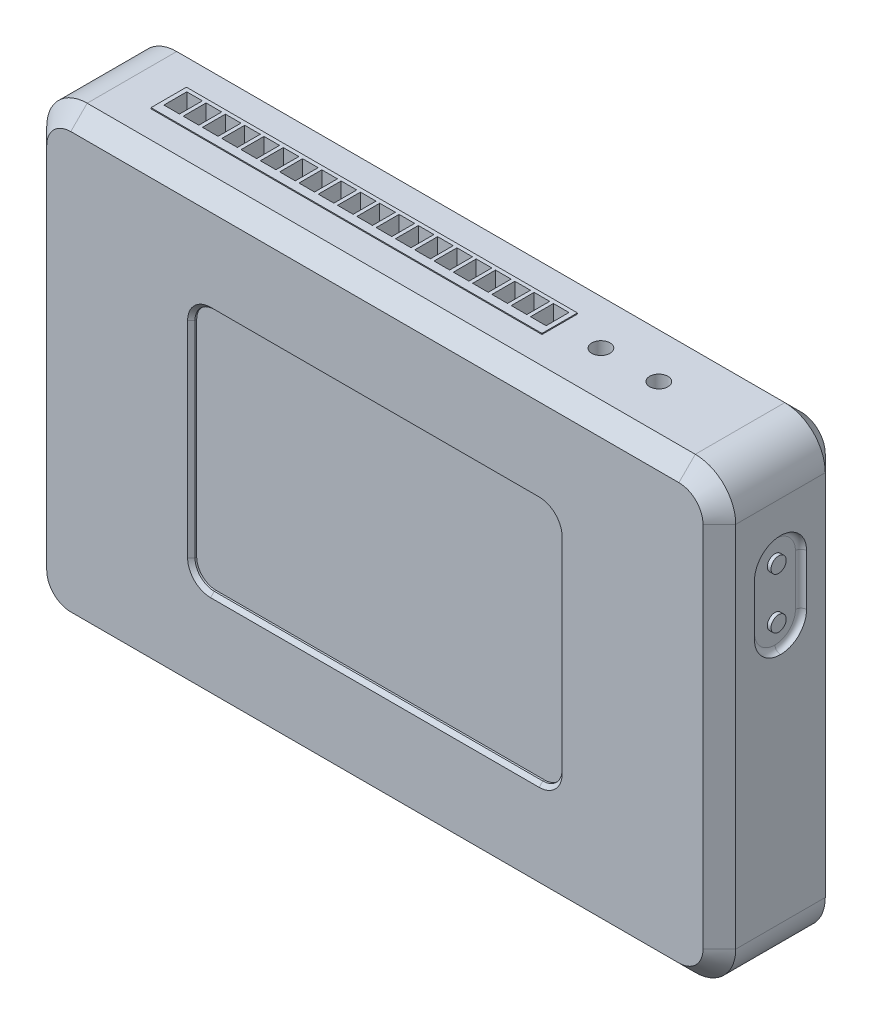
SolidWorks part; units mm, degrees
ref_plane "Top Plane" through (0, 0, 0) normal (0, 0, 1) x (1, 0, 0)
ref_plane "Front Plane" through (0, 0, 0) normal (0, 1, 0) x (1, 0, 0)
ref_plane "Right Plane" through (0, 0, 0) normal (1, 0, 0) x (0, 0, -1)
sketch "Sketch1" plane through (0, 0, 0) normal (0, 0, 1) x (1, 0, 0)
  line L1 (-68.0234, -44.3061) -> (68.0234, -44.3061)
  line L2 (-68.0234, -44.3061) -> (-68.0234, 44.3061)
  line L3 (-68.0234, 44.3061) -> (68.0234, 44.3061)
  line L4 (68.0234, -44.3061) -> (68.0234, 44.3061)
  line L5 (-68.0234, -44.3061) -> (68.0234, 44.3061) construction
  line L6 (-68.0234, 44.3061) -> (68.0234, -44.3061) construction
  point P0 (0, 0)
  dimension "D1" = 88.6122
  dimension "D2" = 136.0469
extrude "Boss-Extrude1" add sketch "Sketch1" along normal mid plane 24.1427
fillet "Fillet1" radius 7.9882 4 edges at (-68.0234, -44.3061, 0) (-68.0234, 44.3061, 0) (68.0234, 44.3061, 0) (68.0234, -44.3061, 0)
chamfer "Chamfer1" distance 3.2329 angle 45 16 edges at (0, 44.3061, -12.0713) (-65.6837, 41.9664, -12.0713) (65.6837, 41.9664, -12.0713) (-68.0234, 0, -12.0713) (68.0234, 0, -12.0713) (-65.6837, -41.9664, -12.0713) (65.6837, -41.9664, -12.0713) (0, -44.3061, -12.0713) (0, 44.3061, 12.0713) (-65.6837, 41.9664, 12.0713) (65.6837, 41.9664, 12.0713) (-68.0234, 0, 12.0713) (68.0234, 0, 12.0713) (-65.6837, -41.9664, 12.0713) (65.6837, -41.9664, 12.0713) (0, -44.3061, 12.0713)
sketch "Sketch2" plane through (68.0234, 0, 0) normal (1, 0, 0) x (0, 0, -1)
  line L0 (0, 0) -> (0, 50000) construction
  line L1 (5.1435, 9.6288) -> (-5.1435, 9.6288)
  line L2 (5.1435, 9.6288) -> (5.1435, 29.9743)
  line L3 (5.1435, 29.9743) -> (-5.1435, 29.9743)
  line L4 (-5.1435, 9.6288) -> (-5.1435, 29.9743)
  line L5 (5.1435, 9.6288) -> (-5.1435, 29.9743) construction
  line L6 (5.1435, 29.9743) -> (-5.1435, 9.6288) construction
  line L7 (8.8385, -44.3061) -> (-8.8385, -44.3061) construction
  line L8 (8.8385, -44.3061) -> (-8.8385, -44.3061) construction
  circle A0 centre (0, 14.7723) radius 1.5 construction
  arc A1 (-5.1435, 14.7723) -> (0, 9.6288) centre (0, 14.7723) ccw construction
  point P0 (0, 19.8015)
  point P14 (-5.1435, 16.5564)
  dimension "D3" = 3
  dimension "D1" = 10.287
  dimension "D2" = 64.1076
  dimension "D4" = 5.0292
extrude "Cut-Extrude1" cut sketch "Sketch2" against normal blind 1.1006
fillet "Fillet2" radius 5.1435 4 edges at (67.4731, 9.6288, -5.1435) (67.4731, 29.9743, -5.1435) (67.4731, 29.9743, 5.1435) (67.4731, 9.6288, 5.1435)
fillet "Fillet3" radius 1.1006 6 edges at (66.9228, 28.4678, 3.637) (66.9228, 28.4678, -3.637) (66.9228, 19.8015, -5.1435) (66.9228, 11.1353, -3.637) (66.9228, 11.1353, 3.637) (66.9228, 19.8015, 5.1435)
sketch "Sketch3" plane through (66.9228, 0, 0) normal (1, 0, 0) x (0, 0, -1)
  line L0 (0, 0) -> (0, 24.8307) construction
  line L1 (-4.0429, 19.8015) -> (4.0429, 19.8015) construction
  line L2 (-4.0429, 24.8307) -> (-4.0429, 14.7723) construction
  line L3 (4.0429, 14.7723) -> (4.0429, 24.8307) construction
  circle A0 centre (0, 24.8307) radius 1.5
  circle A1 centre (0, 14.7723) radius 1.5
  point P12 (0, 0)
  dimension "D1" = 3
  dimension "D2" = 10.0584
extrude "Boss-Extrude2" add sketch "Sketch3" along normal blind 0.7306
sketch "Sketch4" plane through (0, 44.3061, 0) normal (0, 1, 0) x (1, 0, 0)
  line L0 (0, 0) -> (-50000, 0) construction
  line L1 (68.0234, 8.8385) -> (68.0234, -8.8385) construction
  line L2 (68.0234, 8.8385) -> (68.0234, -8.8385) construction
  circle A0 centre (43.9924, 0) radius 1.8
  circle A1 centre (32.5624, 0) radius 1.8
  dimension "D1" = 3.6
  dimension "D2" = 11.43
  dimension "D3" = 24.031
extrude "Cut-Extrude2" cut sketch "Sketch4" against normal blind 2.54
sketch "Sketch5" plane through (0, 0, 12.0713) normal (0, 0, 1) x (1, 0, 0)
  line L1 (36.2458, 24.1046) -> (-36.2458, 24.1046)
  line L2 (36.2458, 24.1046) -> (36.2458, -24.1046)
  line L3 (36.2458, -24.1046) -> (-36.2458, -24.1046)
  line L4 (-36.2458, 24.1046) -> (-36.2458, -24.1046)
  line L5 (36.2458, 24.1046) -> (-36.2458, -24.1046) construction
  line L6 (36.2458, -24.1046) -> (-36.2458, 24.1046) construction
  point P0 (0, 0)
  dimension "D1" = 48.2092
  dimension "D2" = 72.4916
extrude "Cut-Extrude3" cut sketch "Sketch5" against normal blind 1.0668
fillet "Fillet4" radius 3.81 4 edges at (36.2458, -24.1046, 11.538) (36.2458, 24.1046, 11.538) (-36.2458, 24.1046, 11.538) (-36.2458, -24.1046, 11.538)
chamfer "Chamfer2" distance 0.7247 angle 45 8 edges at (0, 24.1046, 12.0713) (-35.1299, 22.9887, 12.0713) (35.1299, 22.9887, 12.0713) (-36.2458, 0, 12.0713) (36.2458, 0, 12.0713) (-35.1299, -22.9887, 12.0713) (35.1299, -22.9887, 12.0713) (0, -24.1046, 12.0713)
sketch "Sketch6" plane through (0, 44.3061, 0) normal (0, 1, 0) x (1, 0, 0)
  line L0 (0, 0) -> (-14.1766, 0) construction
  line L1 (68.0234, 8.8385) -> (68.0234, -8.8385) construction
  line L2 (24.4234, 3.5) -> (-52.7766, 3.5)
  line L3 (24.4234, 3.5) -> (24.4234, -3.5)
  line L4 (24.4234, -3.5) -> (-52.7766, -3.5)
  line L5 (-52.7766, 3.5) -> (-52.7766, -3.5)
  line L6 (24.4234, 3.5) -> (-52.7766, -3.5) construction
  line L7 (24.4234, -3.5) -> (-52.7766, 3.5) construction
  line L8 (68.0234, 8.8385) -> (68.0234, -8.8385) construction
  dimension "D1" = 77.2
  dimension "D2" = 7
  dimension "D3" = 43.6
extrude "Boss-Extrude3" add sketch "Sketch6" along normal blind 0.2
sketch "Sketch7" plane through (0, 44.5061, 0) normal (0, 1, 0) x (1, 0, 0)
  line L0 (0, 0) -> (-50000, 0) construction
  line L1 (24.4234, -3.5) -> (24.4234, 3.5) construction
  line L2 (24.4234, -3.5) -> (24.4234, 3.5) construction
  line L3 (24.4234, 3.5) -> (-52.7766, 3.5) construction
  line L4 (20.4434, -1.782) -> (23.5234, -1.782)
  line L5 (20.4434, -1.782) -> (20.4434, 2.738)
  line L6 (20.4434, 2.738) -> (23.5234, 2.738)
  line L7 (23.5234, -1.782) -> (23.5234, 2.738)
  line L8 (24.4234, 3.5) -> (-52.7766, 3.5) construction
  line L9 (16.6334, -1.782) -> (19.7134, -1.782)
  line L10 (16.6334, -1.782) -> (16.6334, 2.738)
  line L11 (19.7134, -1.782) -> (19.7134, 2.738)
  line L12 (16.6334, 2.738) -> (19.7134, 2.738)
  line L13 (12.8234, -1.782) -> (15.9034, -1.782)
  line L14 (12.8234, -1.782) -> (12.8234, 2.738)
  line L15 (15.9034, -1.782) -> (15.9034, 2.738)
  line L16 (12.8234, 2.738) -> (15.9034, 2.738)
  line L17 (9.0134, -1.782) -> (12.0934, -1.782)
  line L18 (9.0134, -1.782) -> (9.0134, 2.738)
  line L19 (12.0934, -1.782) -> (12.0934, 2.738)
  line L20 (9.0134, 2.738) -> (12.0934, 2.738)
  line L21 (5.2034, -1.782) -> (8.2834, -1.782)
  line L22 (5.2034, -1.782) -> (5.2034, 2.738)
  line L23 (8.2834, -1.782) -> (8.2834, 2.738)
  line L24 (5.2034, 2.738) -> (8.2834, 2.738)
  line L25 (1.3934, -1.782) -> (4.4734, -1.782)
  line L26 (1.3934, -1.782) -> (1.3934, 2.738)
  line L27 (4.4734, -1.782) -> (4.4734, 2.738)
  line L28 (1.3934, 2.738) -> (4.4734, 2.738)
  line L29 (-2.4166, -1.782) -> (0.6634, -1.782)
  line L30 (-2.4166, -1.782) -> (-2.4166, 2.738)
  line L31 (0.6634, -1.782) -> (0.6634, 2.738)
  line L32 (-2.4166, 2.738) -> (0.6634, 2.738)
  line L33 (-6.2266, -1.782) -> (-3.1466, -1.782)
  line L34 (-6.2266, -1.782) -> (-6.2266, 2.738)
  line L35 (-3.1466, -1.782) -> (-3.1466, 2.738)
  line L36 (-6.2266, 2.738) -> (-3.1466, 2.738)
  line L37 (-10.0366, -1.782) -> (-6.9566, -1.782)
  line L38 (-10.0366, -1.782) -> (-10.0366, 2.738)
  line L39 (-6.9566, -1.782) -> (-6.9566, 2.738)
  line L40 (-10.0366, 2.738) -> (-6.9566, 2.738)
  line L41 (-13.8466, -1.782) -> (-10.7666, -1.782)
  line L42 (-13.8466, -1.782) -> (-13.8466, 2.738)
  line L43 (-10.7666, -1.782) -> (-10.7666, 2.738)
  line L44 (-13.8466, 2.738) -> (-10.7666, 2.738)
  line L45 (-17.6566, -1.782) -> (-14.5766, -1.782)
  line L46 (-17.6566, -1.782) -> (-17.6566, 2.738)
  line L47 (-14.5766, -1.782) -> (-14.5766, 2.738)
  line L48 (-17.6566, 2.738) -> (-14.5766, 2.738)
  line L49 (-21.4666, -1.782) -> (-18.3866, -1.782)
  line L50 (-21.4666, -1.782) -> (-21.4666, 2.738)
  line L51 (-18.3866, -1.782) -> (-18.3866, 2.738)
  line L52 (-21.4666, 2.738) -> (-18.3866, 2.738)
  line L53 (-25.2766, -1.782) -> (-22.1966, -1.782)
  line L54 (-25.2766, -1.782) -> (-25.2766, 2.738)
  line L55 (-22.1966, -1.782) -> (-22.1966, 2.738)
  line L56 (-25.2766, 2.738) -> (-22.1966, 2.738)
  line L57 (-29.0866, -1.782) -> (-26.0066, -1.782)
  line L58 (-29.0866, -1.782) -> (-29.0866, 2.738)
  line L59 (-26.0066, -1.782) -> (-26.0066, 2.738)
  line L60 (-29.0866, 2.738) -> (-26.0066, 2.738)
  line L61 (-32.8966, -1.782) -> (-29.8166, -1.782)
  line L62 (-32.8966, -1.782) -> (-32.8966, 2.738)
  line L63 (-29.8166, -1.782) -> (-29.8166, 2.738)
  line L64 (-32.8966, 2.738) -> (-29.8166, 2.738)
  line L65 (-36.7066, -1.782) -> (-33.6266, -1.782)
  line L66 (-36.7066, -1.782) -> (-36.7066, 2.738)
  line L67 (-33.6266, -1.782) -> (-33.6266, 2.738)
  line L68 (-36.7066, 2.738) -> (-33.6266, 2.738)
  line L69 (-40.5166, -1.782) -> (-37.4366, -1.782)
  line L70 (-40.5166, -1.782) -> (-40.5166, 2.738)
  line L71 (-37.4366, -1.782) -> (-37.4366, 2.738)
  line L72 (-40.5166, 2.738) -> (-37.4366, 2.738)
  line L73 (-44.3266, -1.782) -> (-41.2466, -1.782)
  line L74 (-44.3266, -1.782) -> (-44.3266, 2.738)
  line L75 (-41.2466, -1.782) -> (-41.2466, 2.738)
  line L76 (-44.3266, 2.738) -> (-41.2466, 2.738)
  line L77 (-48.1366, -1.782) -> (-45.0566, -1.782)
  line L78 (-48.1366, -1.782) -> (-48.1366, 2.738)
  line L79 (-45.0566, -1.782) -> (-45.0566, 2.738)
  line L80 (-48.1366, 2.738) -> (-45.0566, 2.738)
  line L81 (-51.9466, -1.782) -> (-48.8666, -1.782)
  line L82 (-51.9466, -1.782) -> (-51.9466, 2.738)
  line L83 (-48.8666, -1.782) -> (-48.8666, 2.738)
  line L84 (-51.9466, 2.738) -> (-48.8666, 2.738)
  line L85 (18.1734, -1.782) -> (18.1734, 2.738) construction
  line L86 (21.9834, 2.738) -> (21.9834, -1.782) construction
  dimension "D1" = 3.08
  dimension "D2" = 4.52
  dimension "D3" = 0.9
  dimension "D4" = 0.762
  dimension "D6" = 3.81
  dimension "D5" = 20
extrude "Cut-Extrude4" cut sketch "Sketch7" against normal blind 6.95
sketch "Sketch8" plane through (0, 37.5561, 0) normal (0, 1, 0) x (1, 0, 0)
  line L0 (21.9834, -1.782) -> (21.9834, 2.738) construction
  line L1 (20.4434, -1.782) -> (23.5234, -1.782) construction
  line L2 (23.5234, 2.738) -> (20.4434, 2.738) construction
  line L3 (20.4434, 0.478) -> (21.9834, 0.478) construction
  line L4 (20.4434, 2.738) -> (20.4434, -1.782) construction
  line L5 (18.5734, 0.878) -> (17.7734, 0.878)
  line L6 (22.3834, 0.878) -> (21.5834, 0.878)
  line L7 (22.3834, 0.878) -> (22.3834, 0.078)
  line L8 (22.3834, 0.078) -> (21.5834, 0.078)
  line L9 (21.5834, 0.878) -> (21.5834, 0.078)
  line L10 (22.3834, 0.878) -> (21.5834, 0.078) construction
  line L11 (22.3834, 0.078) -> (21.5834, 0.878) construction
  line L12 (18.5734, 0.878) -> (18.5734, 0.078)
  line L13 (18.5734, 0.078) -> (17.7734, 0.078)
  line L14 (17.7734, 0.878) -> (17.7734, 0.078)
  line L15 (16.6334, 0.478) -> (18.1734, 0.478) construction
  line L16 (18.5734, 0.878) -> (17.7734, 0.078) construction
  line L17 (18.5734, 0.078) -> (17.7734, 0.878) construction
  line L18 (14.7634, 0.878) -> (13.9634, 0.878)
  line L19 (14.7634, 0.878) -> (14.7634, 0.078)
  line L20 (14.7634, 0.078) -> (13.9634, 0.078)
  line L21 (13.9634, 0.878) -> (13.9634, 0.078)
  line L22 (12.8234, 0.478) -> (14.3634, 0.478) construction
  line L23 (14.7634, 0.878) -> (13.9634, 0.078) construction
  line L24 (14.7634, 0.078) -> (13.9634, 0.878) construction
  line L25 (10.9534, 0.878) -> (10.1534, 0.878)
  line L26 (10.9534, 0.878) -> (10.9534, 0.078)
  line L27 (10.9534, 0.078) -> (10.1534, 0.078)
  line L28 (10.1534, 0.878) -> (10.1534, 0.078)
  line L29 (9.0134, 0.478) -> (10.5534, 0.478) construction
  line L30 (10.9534, 0.878) -> (10.1534, 0.078) construction
  line L31 (10.9534, 0.078) -> (10.1534, 0.878) construction
  line L32 (7.1434, 0.878) -> (6.3434, 0.878)
  line L33 (7.1434, 0.878) -> (7.1434, 0.078)
  line L34 (7.1434, 0.078) -> (6.3434, 0.078)
  line L35 (6.3434, 0.878) -> (6.3434, 0.078)
  line L36 (5.2034, 0.478) -> (6.7434, 0.478) construction
  line L37 (7.1434, 0.878) -> (6.3434, 0.078) construction
  line L38 (7.1434, 0.078) -> (6.3434, 0.878) construction
  line L39 (3.3334, 0.878) -> (2.5334, 0.878)
  line L40 (3.3334, 0.878) -> (3.3334, 0.078)
  line L41 (3.3334, 0.078) -> (2.5334, 0.078)
  line L42 (2.5334, 0.878) -> (2.5334, 0.078)
  line L43 (1.3934, 0.478) -> (2.9334, 0.478) construction
  line L44 (3.3334, 0.878) -> (2.5334, 0.078) construction
  line L45 (3.3334, 0.078) -> (2.5334, 0.878) construction
  line L46 (-0.4766, 0.878) -> (-1.2766, 0.878)
  line L47 (-0.4766, 0.878) -> (-0.4766, 0.078)
  line L48 (-0.4766, 0.078) -> (-1.2766, 0.078)
  line L49 (-1.2766, 0.878) -> (-1.2766, 0.078)
  line L50 (-2.4166, 0.478) -> (-0.8766, 0.478) construction
  line L51 (-0.4766, 0.878) -> (-1.2766, 0.078) construction
  line L52 (-0.4766, 0.078) -> (-1.2766, 0.878) construction
  line L53 (-4.2866, 0.878) -> (-5.0866, 0.878)
  line L54 (-4.2866, 0.878) -> (-4.2866, 0.078)
  line L55 (-4.2866, 0.078) -> (-5.0866, 0.078)
  line L56 (-5.0866, 0.878) -> (-5.0866, 0.078)
  line L57 (-6.2266, 0.478) -> (-4.6866, 0.478) construction
  line L58 (-4.2866, 0.878) -> (-5.0866, 0.078) construction
  line L59 (-4.2866, 0.078) -> (-5.0866, 0.878) construction
  line L60 (-8.0966, 0.878) -> (-8.8966, 0.878)
  line L61 (-8.0966, 0.878) -> (-8.0966, 0.078)
  line L62 (-8.0966, 0.078) -> (-8.8966, 0.078)
  line L63 (-8.8966, 0.878) -> (-8.8966, 0.078)
  line L64 (-10.0366, 0.478) -> (-8.4966, 0.478) construction
  line L65 (-8.0966, 0.878) -> (-8.8966, 0.078) construction
  line L66 (-8.0966, 0.078) -> (-8.8966, 0.878) construction
  line L67 (-11.9066, 0.878) -> (-12.7066, 0.878)
  line L68 (-11.9066, 0.878) -> (-11.9066, 0.078)
  line L69 (-11.9066, 0.078) -> (-12.7066, 0.078)
  line L70 (-12.7066, 0.878) -> (-12.7066, 0.078)
  line L71 (-13.8466, 0.478) -> (-12.3066, 0.478) construction
  line L72 (-11.9066, 0.878) -> (-12.7066, 0.078) construction
  line L73 (-11.9066, 0.078) -> (-12.7066, 0.878) construction
  line L74 (-15.7166, 0.878) -> (-16.5166, 0.878)
  line L75 (-15.7166, 0.878) -> (-15.7166, 0.078)
  line L76 (-15.7166, 0.078) -> (-16.5166, 0.078)
  line L77 (-16.5166, 0.878) -> (-16.5166, 0.078)
  line L78 (-17.6566, 0.478) -> (-16.1166, 0.478) construction
  line L79 (-15.7166, 0.878) -> (-16.5166, 0.078) construction
  line L80 (-15.7166, 0.078) -> (-16.5166, 0.878) construction
  line L81 (-19.5266, 0.878) -> (-20.3266, 0.878)
  line L82 (-19.5266, 0.878) -> (-19.5266, 0.078)
  line L83 (-19.5266, 0.078) -> (-20.3266, 0.078)
  line L84 (-20.3266, 0.878) -> (-20.3266, 0.078)
  line L85 (-21.4666, 0.478) -> (-19.9266, 0.478) construction
  line L86 (-19.5266, 0.878) -> (-20.3266, 0.078) construction
  line L87 (-19.5266, 0.078) -> (-20.3266, 0.878) construction
  line L88 (-23.3366, 0.878) -> (-24.1366, 0.878)
  line L89 (-23.3366, 0.878) -> (-23.3366, 0.078)
  line L90 (-23.3366, 0.078) -> (-24.1366, 0.078)
  line L91 (-24.1366, 0.878) -> (-24.1366, 0.078)
  line L92 (-25.2766, 0.478) -> (-23.7366, 0.478) construction
  line L93 (-23.3366, 0.878) -> (-24.1366, 0.078) construction
  line L94 (-23.3366, 0.078) -> (-24.1366, 0.878) construction
  line L95 (-27.1466, 0.878) -> (-27.9466, 0.878)
  line L96 (-27.1466, 0.878) -> (-27.1466, 0.078)
  line L97 (-27.1466, 0.078) -> (-27.9466, 0.078)
  line L98 (-27.9466, 0.878) -> (-27.9466, 0.078)
  line L99 (-29.0866, 0.478) -> (-27.5466, 0.478) construction
  line L100 (-27.1466, 0.878) -> (-27.9466, 0.078) construction
  line L101 (-27.1466, 0.078) -> (-27.9466, 0.878) construction
  line L102 (-30.9566, 0.878) -> (-31.7566, 0.878)
  line L103 (-30.9566, 0.878) -> (-30.9566, 0.078)
  line L104 (-30.9566, 0.078) -> (-31.7566, 0.078)
  line L105 (-31.7566, 0.878) -> (-31.7566, 0.078)
  line L106 (-32.8966, 0.478) -> (-31.3566, 0.478) construction
  line L107 (-30.9566, 0.878) -> (-31.7566, 0.078) construction
  line L108 (-30.9566, 0.078) -> (-31.7566, 0.878) construction
  line L109 (-34.7666, 0.878) -> (-35.5666, 0.878)
  line L110 (-34.7666, 0.878) -> (-34.7666, 0.078)
  line L111 (-34.7666, 0.078) -> (-35.5666, 0.078)
  line L112 (-35.5666, 0.878) -> (-35.5666, 0.078)
  line L113 (-36.7066, 0.478) -> (-35.1666, 0.478) construction
  line L114 (-34.7666, 0.878) -> (-35.5666, 0.078) construction
  line L115 (-34.7666, 0.078) -> (-35.5666, 0.878) construction
  line L116 (-38.5766, 0.878) -> (-39.3766, 0.878)
  line L117 (-38.5766, 0.878) -> (-38.5766, 0.078)
  line L118 (-38.5766, 0.078) -> (-39.3766, 0.078)
  line L119 (-39.3766, 0.878) -> (-39.3766, 0.078)
  line L120 (-40.5166, 0.478) -> (-38.9766, 0.478) construction
  line L121 (-38.5766, 0.878) -> (-39.3766, 0.078) construction
  line L122 (-38.5766, 0.078) -> (-39.3766, 0.878) construction
  line L123 (-42.3866, 0.878) -> (-43.1866, 0.878)
  line L124 (-42.3866, 0.878) -> (-42.3866, 0.078)
  line L125 (-42.3866, 0.078) -> (-43.1866, 0.078)
  line L126 (-43.1866, 0.878) -> (-43.1866, 0.078)
  line L127 (-44.3266, 0.478) -> (-42.7866, 0.478) construction
  line L128 (-42.3866, 0.878) -> (-43.1866, 0.078) construction
  line L129 (-42.3866, 0.078) -> (-43.1866, 0.878) construction
  line L130 (-46.1966, 0.878) -> (-46.9966, 0.878)
  line L131 (-46.1966, 0.878) -> (-46.1966, 0.078)
  line L132 (-46.1966, 0.078) -> (-46.9966, 0.078)
  line L133 (-46.9966, 0.878) -> (-46.9966, 0.078)
  line L134 (-48.1366, 0.478) -> (-46.5966, 0.478) construction
  line L135 (-46.1966, 0.878) -> (-46.9966, 0.078) construction
  line L136 (-46.1966, 0.078) -> (-46.9966, 0.878) construction
  line L137 (-50.0066, 0.878) -> (-50.8066, 0.878)
  line L138 (-50.0066, 0.878) -> (-50.0066, 0.078)
  line L139 (-50.0066, 0.078) -> (-50.8066, 0.078)
  line L140 (-50.8066, 0.878) -> (-50.8066, 0.078)
  line L141 (-51.9466, 0.478) -> (-50.4066, 0.478) construction
  line L142 (-50.0066, 0.878) -> (-50.8066, 0.078) construction
  line L143 (-50.0066, 0.078) -> (-50.8066, 0.878) construction
  point P132 (-53.573, 0.3406)
  point P133 (18.021, 0.2276)
  dimension "D1" = 0.8
  dimension "D3" = 3.81
  dimension "D2" = 20
extrude "Boss-Extrude4" add sketch "Sketch8" along normal blind 4.3
sketch "Sketch9" plane through (0, 0, -12.0713) normal (0, 0, -1) x (-1, 0, 0)
  line L0 (0, 0) -> (50000, 0) construction
  line L1 (44.7766, 0) -> (44.7766, 50000) construction
  line L2 (-68.0234, -36.3179) -> (-68.0234, 36.3179) construction
  line L3 (-68.0234, -36.3179) -> (-68.0234, 36.3179) construction
  circle A0 centre (44.7766, 22.1) radius 1.6319
  circle A1 centre (44.7766, -22.1) radius 1.6319
  circle A2 centre (-35.2234, 0) radius 1.6319
  point P11 (0, 0)
  dimension "D1" = 3.2639
  dimension "D2" = 44.2
  dimension "D3" = 80
  dimension "D4" = 32.8
extrude "Cut-Extrude5" cut sketch "Sketch9" against normal blind 2.54
sketch "Sketch10" plane through (-68.0234, 0, 0) normal (-1, 0, 0) x (0, 0, 1)
  line L0 (0, 0) -> (0, -50000) construction
  line L1 (-8.8385, 44.3061) -> (8.8385, 44.3061) construction
  line L2 (-8.8385, 44.3061) -> (8.8385, 44.3061) construction
  line L3 (8.8385, -44.3061) -> (-8.8385, -44.3061) construction
  line L4 (8.8385, -44.3061) -> (-8.8385, -44.3061) construction
  line L6 (-2.8359, 25.9701) -> (2.8359, 25.9701)
  line L7 (-2.8359, 25.9701) -> (-2.8359, 13.4101)
  line L8 (-2.8359, 13.4101) -> (2.8359, 13.4101)
  line L9 (2.8359, 25.9701) -> (2.8359, 13.4101)
  line L10 (-2.8359, 25.9701) -> (2.8359, 13.4101) construction
  line L11 (-2.8359, 13.4101) -> (2.8359, 25.9701) construction
  line L12 (5.5969, 7.2661) -> (-2.8359, 7.2661)
  line L13 (5.5969, 7.2661) -> (5.5969, -2.0339)
  line L14 (5.5969, -2.0339) -> (-2.8359, -2.0339)
  line L15 (-2.8359, 7.2661) -> (-2.8359, -2.0339)
  line L16 (5.5969, 7.2661) -> (-2.8359, -2.0339) construction
  line L17 (5.5969, -2.0339) -> (-2.8359, 7.2661) construction
  point P7 (0, 19.6901)
  point P12 (1.3805, 2.6161)
  dimension "D1" = 12.56
  dimension "D2" = 5.6718
  dimension "D3" = 18.336
  dimension "D4" = 8.4328
  dimension "D5" = 9.3
  dimension "D7" = 37.04
extrude "Cut-Extrude6" cut sketch "Sketch10" against normal blind 6.35
chamfer "Chamfer3" distance 2.1866 angle 45 2 edges at (-64.8484, 7.2661, 5.5969) (-64.8484, -2.0339, 5.5969)
sketch "Sketch11" plane through (-68.0234, 0, 0) normal (-1, 0, 0) x (0, 0, 1)
  line L0 (0, 0) -> (0, -50.5969) construction
  line L1 (8.8385, -44.3061) -> (-8.8385, -44.3061) construction
  line L2 (8.8385, -44.3061) -> (-8.8385, -44.3061) construction
  line L4 (7, -7.8261) -> (-4, -7.8261)
  line L5 (7, -7.8261) -> (7, -16.8261)
  line L6 (7, -16.8261) -> (-4, -16.8261)
  line L7 (-4, -7.8261) -> (-4, -16.8261)
  line L8 (7, -7.8261) -> (-4, -16.8261) construction
  line L9 (7, -16.8261) -> (-4, -7.8261) construction
  point P5 (1.5, -12.3261)
  point P10 (0, 0)
  dimension "D1" = 9
  dimension "D2" = 11
  dimension "D3" = 4
  dimension "D4" = 31.98
extrude "Boss-Extrude5" add sketch "Sketch11" along normal blind 0.508
sketch "Sketch12" plane through (-68.5314, 0, 0) normal (-1, 0, 0) x (0, 0, 1)
  line L0 (7, -12.3261) -> (-4, -12.3261) construction
  line L1 (7, -16.8261) -> (7, -7.8261) construction
  line L2 (-4, -7.8261) -> (-4, -16.8261) construction
  circle A0 centre (2.5, -12.3261) radius 3.2
  dimension "D1" = 6.4
  dimension "D2" = 4.5
extrude "Cut-Extrude7" cut sketch "Sketch12" against normal blind 10
sketch "Sketch13" plane through (-58.5314, 0, 0) normal (-1, 0, 0) x (0, 0, 1)
  circle A0 centre (2.5, -12.3261) radius 3.2 construction
  circle A1 centre (2.5, -12.3261) radius 3.2 construction
  circle A2 centre (2.5, -12.3261) radius 1
  dimension "D1" = 2
extrude "Boss-Extrude6" add sketch "Sketch13" along normal blind 8
sketch "Sketch14" plane through (-68.0234, 0, 0) normal (-1, 0, 0) x (0, 0, 1)
  line L0 (0, 0) -> (0, -40.8079) construction
  line L1 (8.8385, -44.3061) -> (-8.8385, -44.3061) construction
  line L2 (8.8385, -44.3061) -> (-8.8385, -44.3061) construction
  circle A0 centre (0, -23.6061) radius 1.778
  dimension "D1" = 3.556
  dimension "D2" = 20.7
extrude "Cut-Extrude8" cut sketch "Sketch14" against normal blind 2.75
sketch "Sketch15" plane through (0, -44.3061, 0) normal (0, -1, 0) x (1, 0, 0)
  line L0 (-68.0234, -8.8385) -> (-68.0234, 8.8385) construction
  line L1 (-68.0234, -8.8385) -> (-68.0234, 8.8385) construction
  line L2 (0, 0) -> (50000, 0) construction
  line L3 (3.4646, -2.5) -> (54.2646, -2.5)
  line L4 (-53.6854, -2.5) -> (-2.8854, -2.5)
  line L5 (-53.6854, -2.5) -> (-53.6854, 6.3)
  line L6 (-53.6854, 6.3) -> (-2.8854, 6.3)
  line L7 (-2.8854, -2.5) -> (-2.8854, 6.3)
  line L8 (3.4646, -2.5) -> (3.4646, 6.3)
  line L9 (3.4646, 6.3) -> (54.2646, 6.3)
  line L10 (54.2646, -2.5) -> (54.2646, 6.3)
  dimension "D1" = 14.338
  dimension "D2" = 2.5
  dimension "D3" = 8.8
  dimension "D4" = 50.8
  dimension "D5" = 2
extrude "Boss-Extrude7" add sketch "Sketch15" along normal blind 0.25
sketch "Sketch16" plane through (0, -44.5561, 0) normal (0, -1, 0) x (1, 0, 0)
  line L0 (-28.2854, 6.3) -> (-28.2854, -2.5) construction
  line L1 (-2.8854, 6.3) -> (-53.6854, 6.3) construction
  line L2 (-53.6854, -2.5) -> (-2.8854, -2.5) construction
  line L3 (-53.6854, 1.9) -> (-2.8854, 1.9) construction
  line L4 (-53.6854, 6.3) -> (-53.6854, -2.5) construction
  line L5 (-2.8854, -2.5) -> (-2.8854, 6.3) construction
  line L6 (4.5198, 5.1) -> (26.6146, 5.1)
  line L7 (-52.5354, -1.3) -> (-4.0354, -1.3)
  line L8 (-52.5354, -1.3) -> (-52.5354, 5.1)
  line L9 (-52.5354, 5.1) -> (-30.5354, 5.1)
  line L10 (-4.0354, -1.3) -> (-4.0354, 5.1)
  line L11 (-52.5354, -1.3) -> (-4.0354, 5.1) construction
  line L12 (-52.5354, 5.1) -> (-4.0354, -1.3) construction
  line L13 (53.0198, -1.3) -> (53.0198, 5.1)
  line L14 (4.5198, -1.3) -> (53.0198, -1.3)
  line L15 (4.5198, -1.3) -> (4.5198, 5.1)
  line L16 (-26.0354, 5.1) -> (-4.0354, 5.1)
  line L17 (28.8646, -2.5) -> (28.8646, 6.3) construction
  line L18 (-30.5354, 5.1) -> (-30.5354, 6.3)
  line L19 (-30.5354, 6.3) -> (-26.0354, 6.3)
  line L20 (-26.0354, 5.1) -> (-26.0354, 6.3)
  line L21 (3.4646, -2.5) -> (54.2646, -2.5) construction
  line L22 (54.2646, 6.3) -> (3.4646, 6.3) construction
  line L23 (31.1146, 5.1) -> (53.0198, 5.1)
  line L24 (26.6146, 6.3) -> (31.1146, 6.3)
  line L25 (26.6146, 6.3) -> (26.6146, 5.1)
  line L27 (31.1146, 6.3) -> (31.1146, 5.1)
  point P12 (-28.2854, 1.9)
  dimension "D1" = 48.5
  dimension "D2" = 6.4
  dimension "D4" = 4.5
  dimension "D5" = 4.5
  dimension "D3" = 2
extrude "Cut-Extrude9" cut sketch "Sketch16" against normal blind 6.25
sketch "Sketch17" plane through (0, -38.3061, 0) normal (0, -1, 0) x (1, 0, 0)
  line L0 (-30.5354, 5.1) -> (-26.0354, 5.1) construction
  line L1 (-28.2854, 5.1) -> (-28.2854, -1.3) construction
  line L2 (-52.5354, -1.3) -> (-4.0354, -1.3) construction
  line L3 (-28.2854, 1.9) -> (49971.7146, 1.9) construction
  line L4 (-26.0654, 3.49) -> (-25.4254, 3.49)
  line L5 (-28.6054, 3.49) -> (-27.9654, 3.49)
  line L6 (-28.6054, 3.49) -> (-28.6054, 2.85)
  line L7 (-28.6054, 2.85) -> (-27.9654, 2.85)
  line L8 (-27.9654, 3.49) -> (-27.9654, 2.85)
  line L9 (-28.6054, 3.49) -> (-27.9654, 2.85) construction
  line L10 (-28.6054, 2.85) -> (-27.9654, 3.49) construction
  line L11 (-28.6054, 0.95) -> (-27.9654, 0.95)
  line L12 (-28.6054, 0.95) -> (-28.6054, 0.31)
  line L13 (-28.6054, 0.31) -> (-27.9654, 0.31)
  line L14 (-27.9654, 0.95) -> (-27.9654, 0.31)
  line L15 (-28.6054, 0.95) -> (-27.9654, 0.31) construction
  line L16 (-28.6054, 0.31) -> (-27.9654, 0.95) construction
  line L17 (-26.0654, 3.49) -> (-26.0654, 2.85)
  line L18 (-26.0654, 2.85) -> (-25.4254, 2.85)
  line L19 (-25.4254, 3.49) -> (-25.4254, 2.85)
  line L20 (-26.0654, 0.95) -> (-25.4254, 0.95)
  line L21 (-26.0654, 0.95) -> (-26.0654, 0.31)
  line L22 (-26.0654, 0.31) -> (-25.4254, 0.31)
  line L23 (-25.4254, 0.95) -> (-25.4254, 0.31)
  line L24 (-26.0654, 3.49) -> (-25.4254, 2.85) construction
  line L25 (-26.0654, 2.85) -> (-25.4254, 3.49) construction
  line L26 (-26.0654, 0.95) -> (-25.4254, 0.31) construction
  line L27 (-26.0654, 0.31) -> (-25.4254, 0.95) construction
  line L28 (-23.5254, 3.49) -> (-22.8854, 3.49)
  line L29 (-23.5254, 3.49) -> (-23.5254, 2.85)
  line L30 (-23.5254, 2.85) -> (-22.8854, 2.85)
  line L31 (-22.8854, 3.49) -> (-22.8854, 2.85)
  line L32 (-23.5254, 0.95) -> (-22.8854, 0.95)
  line L33 (-23.5254, 0.95) -> (-23.5254, 0.31)
  line L34 (-23.5254, 0.31) -> (-22.8854, 0.31)
  line L35 (-22.8854, 0.95) -> (-22.8854, 0.31)
  line L36 (-23.5254, 3.49) -> (-22.8854, 2.85) construction
  line L37 (-23.5254, 2.85) -> (-22.8854, 3.49) construction
  line L38 (-23.5254, 0.95) -> (-22.8854, 0.31) construction
  line L39 (-23.5254, 0.31) -> (-22.8854, 0.95) construction
  line L40 (-20.9854, 3.49) -> (-20.3454, 3.49)
  line L41 (-20.9854, 3.49) -> (-20.9854, 2.85)
  line L42 (-20.9854, 2.85) -> (-20.3454, 2.85)
  line L43 (-20.3454, 3.49) -> (-20.3454, 2.85)
  line L44 (-20.9854, 0.95) -> (-20.3454, 0.95)
  line L45 (-20.9854, 0.95) -> (-20.9854, 0.31)
  line L46 (-20.9854, 0.31) -> (-20.3454, 0.31)
  line L47 (-20.3454, 0.95) -> (-20.3454, 0.31)
  line L48 (-20.9854, 3.49) -> (-20.3454, 2.85) construction
  line L49 (-20.9854, 2.85) -> (-20.3454, 3.49) construction
  line L50 (-20.9854, 0.95) -> (-20.3454, 0.31) construction
  line L51 (-20.9854, 0.31) -> (-20.3454, 0.95) construction
  line L52 (-18.4454, 3.49) -> (-17.8054, 3.49)
  line L53 (-18.4454, 3.49) -> (-18.4454, 2.85)
  line L54 (-18.4454, 2.85) -> (-17.8054, 2.85)
  line L55 (-17.8054, 3.49) -> (-17.8054, 2.85)
  line L56 (-18.4454, 0.95) -> (-17.8054, 0.95)
  line L57 (-18.4454, 0.95) -> (-18.4454, 0.31)
  line L58 (-18.4454, 0.31) -> (-17.8054, 0.31)
  line L59 (-17.8054, 0.95) -> (-17.8054, 0.31)
  line L60 (-18.4454, 3.49) -> (-17.8054, 2.85) construction
  line L61 (-18.4454, 2.85) -> (-17.8054, 3.49) construction
  line L62 (-18.4454, 0.95) -> (-17.8054, 0.31) construction
  line L63 (-18.4454, 0.31) -> (-17.8054, 0.95) construction
  line L64 (-15.9054, 3.49) -> (-15.2654, 3.49)
  line L65 (-15.9054, 3.49) -> (-15.9054, 2.85)
  line L66 (-15.9054, 2.85) -> (-15.2654, 2.85)
  line L67 (-15.2654, 3.49) -> (-15.2654, 2.85)
  line L68 (-15.9054, 0.95) -> (-15.2654, 0.95)
  line L69 (-15.9054, 0.95) -> (-15.9054, 0.31)
  line L70 (-15.9054, 0.31) -> (-15.2654, 0.31)
  line L71 (-15.2654, 0.95) -> (-15.2654, 0.31)
  line L72 (-15.9054, 3.49) -> (-15.2654, 2.85) construction
  line L73 (-15.9054, 2.85) -> (-15.2654, 3.49) construction
  line L74 (-15.9054, 0.95) -> (-15.2654, 0.31) construction
  line L75 (-15.9054, 0.31) -> (-15.2654, 0.95) construction
  line L76 (-13.3654, 3.49) -> (-12.7254, 3.49)
  line L77 (-13.3654, 3.49) -> (-13.3654, 2.85)
  line L78 (-13.3654, 2.85) -> (-12.7254, 2.85)
  line L79 (-12.7254, 3.49) -> (-12.7254, 2.85)
  line L80 (-13.3654, 0.95) -> (-12.7254, 0.95)
  line L81 (-13.3654, 0.95) -> (-13.3654, 0.31)
  line L82 (-13.3654, 0.31) -> (-12.7254, 0.31)
  line L83 (-12.7254, 0.95) -> (-12.7254, 0.31)
  line L84 (-13.3654, 3.49) -> (-12.7254, 2.85) construction
  line L85 (-13.3654, 2.85) -> (-12.7254, 3.49) construction
  line L86 (-13.3654, 0.95) -> (-12.7254, 0.31) construction
  line L87 (-13.3654, 0.31) -> (-12.7254, 0.95) construction
  line L88 (-10.8254, 3.49) -> (-10.1854, 3.49)
  line L89 (-10.8254, 3.49) -> (-10.8254, 2.85)
  line L90 (-10.8254, 2.85) -> (-10.1854, 2.85)
  line L91 (-10.1854, 3.49) -> (-10.1854, 2.85)
  line L92 (-10.8254, 0.95) -> (-10.1854, 0.95)
  line L93 (-10.8254, 0.95) -> (-10.8254, 0.31)
  line L94 (-10.8254, 0.31) -> (-10.1854, 0.31)
  line L95 (-10.1854, 0.95) -> (-10.1854, 0.31)
  line L96 (-10.8254, 3.49) -> (-10.1854, 2.85) construction
  line L97 (-10.8254, 2.85) -> (-10.1854, 3.49) construction
  line L98 (-10.8254, 0.95) -> (-10.1854, 0.31) construction
  line L99 (-10.8254, 0.31) -> (-10.1854, 0.95) construction
  line L100 (-8.2854, 3.49) -> (-7.6454, 3.49)
  line L101 (-8.2854, 3.49) -> (-8.2854, 2.85)
  line L102 (-8.2854, 2.85) -> (-7.6454, 2.85)
  line L103 (-7.6454, 3.49) -> (-7.6454, 2.85)
  line L104 (-8.2854, 0.95) -> (-7.6454, 0.95)
  line L105 (-8.2854, 0.95) -> (-8.2854, 0.31)
  line L106 (-8.2854, 0.31) -> (-7.6454, 0.31)
  line L107 (-7.6454, 0.95) -> (-7.6454, 0.31)
  line L108 (-8.2854, 3.49) -> (-7.6454, 2.85) construction
  line L109 (-8.2854, 2.85) -> (-7.6454, 3.49) construction
  line L110 (-8.2854, 0.95) -> (-7.6454, 0.31) construction
  line L111 (-8.2854, 0.31) -> (-7.6454, 0.95) construction
  line L112 (-31.1454, 3.49) -> (-30.5054, 3.49)
  line L113 (-31.1454, 3.49) -> (-31.1454, 2.85)
  line L114 (-31.1454, 2.85) -> (-30.5054, 2.85)
  line L115 (-30.5054, 3.49) -> (-30.5054, 2.85)
  line L116 (-31.1454, 0.95) -> (-30.5054, 0.95)
  line L117 (-31.1454, 0.95) -> (-31.1454, 0.31)
  line L118 (-31.1454, 0.31) -> (-30.5054, 0.31)
  line L119 (-30.5054, 0.95) -> (-30.5054, 0.31)
  line L120 (-31.1454, 3.49) -> (-30.5054, 2.85) construction
  line L121 (-31.1454, 2.85) -> (-30.5054, 3.49) construction
  line L122 (-31.1454, 0.95) -> (-30.5054, 0.31) construction
  line L123 (-31.1454, 0.31) -> (-30.5054, 0.95) construction
  line L124 (-33.6854, 3.49) -> (-33.0454, 3.49)
  line L125 (-33.6854, 3.49) -> (-33.6854, 2.85)
  line L126 (-33.6854, 2.85) -> (-33.0454, 2.85)
  line L127 (-33.0454, 3.49) -> (-33.0454, 2.85)
  line L128 (-33.6854, 0.95) -> (-33.0454, 0.95)
  line L129 (-33.6854, 0.95) -> (-33.6854, 0.31)
  line L130 (-33.6854, 0.31) -> (-33.0454, 0.31)
  line L131 (-33.0454, 0.95) -> (-33.0454, 0.31)
  line L132 (-33.6854, 3.49) -> (-33.0454, 2.85) construction
  line L133 (-33.6854, 2.85) -> (-33.0454, 3.49) construction
  line L134 (-33.6854, 0.95) -> (-33.0454, 0.31) construction
  line L135 (-33.6854, 0.31) -> (-33.0454, 0.95) construction
  line L136 (-36.2254, 3.49) -> (-35.5854, 3.49)
  line L137 (-36.2254, 3.49) -> (-36.2254, 2.85)
  line L138 (-36.2254, 2.85) -> (-35.5854, 2.85)
  line L139 (-35.5854, 3.49) -> (-35.5854, 2.85)
  line L140 (-36.2254, 0.95) -> (-35.5854, 0.95)
  line L141 (-36.2254, 0.95) -> (-36.2254, 0.31)
  line L142 (-36.2254, 0.31) -> (-35.5854, 0.31)
  line L143 (-35.5854, 0.95) -> (-35.5854, 0.31)
  line L144 (-36.2254, 3.49) -> (-35.5854, 2.85) construction
  line L145 (-36.2254, 2.85) -> (-35.5854, 3.49) construction
  line L146 (-36.2254, 0.95) -> (-35.5854, 0.31) construction
  line L147 (-36.2254, 0.31) -> (-35.5854, 0.95) construction
  line L148 (-38.7654, 3.49) -> (-38.1254, 3.49)
  line L149 (-38.7654, 3.49) -> (-38.7654, 2.85)
  line L150 (-38.7654, 2.85) -> (-38.1254, 2.85)
  line L151 (-38.1254, 3.49) -> (-38.1254, 2.85)
  line L152 (-38.7654, 0.95) -> (-38.1254, 0.95)
  line L153 (-38.7654, 0.95) -> (-38.7654, 0.31)
  line L154 (-38.7654, 0.31) -> (-38.1254, 0.31)
  line L155 (-38.1254, 0.95) -> (-38.1254, 0.31)
  line L156 (-38.7654, 3.49) -> (-38.1254, 2.85) construction
  line L157 (-38.7654, 2.85) -> (-38.1254, 3.49) construction
  line L158 (-38.7654, 0.95) -> (-38.1254, 0.31) construction
  line L159 (-38.7654, 0.31) -> (-38.1254, 0.95) construction
  line L160 (-41.3054, 3.49) -> (-40.6654, 3.49)
  line L161 (-41.3054, 3.49) -> (-41.3054, 2.85)
  line L162 (-41.3054, 2.85) -> (-40.6654, 2.85)
  line L163 (-40.6654, 3.49) -> (-40.6654, 2.85)
  line L164 (-41.3054, 0.95) -> (-40.6654, 0.95)
  line L165 (-41.3054, 0.95) -> (-41.3054, 0.31)
  line L166 (-41.3054, 0.31) -> (-40.6654, 0.31)
  line L167 (-40.6654, 0.95) -> (-40.6654, 0.31)
  line L168 (-41.3054, 3.49) -> (-40.6654, 2.85) construction
  line L169 (-41.3054, 2.85) -> (-40.6654, 3.49) construction
  line L170 (-41.3054, 0.95) -> (-40.6654, 0.31) construction
  line L171 (-41.3054, 0.31) -> (-40.6654, 0.95) construction
  line L172 (-43.8454, 3.49) -> (-43.2054, 3.49)
  line L173 (-43.8454, 3.49) -> (-43.8454, 2.85)
  line L174 (-43.8454, 2.85) -> (-43.2054, 2.85)
  line L175 (-43.2054, 3.49) -> (-43.2054, 2.85)
  line L176 (-43.8454, 0.95) -> (-43.2054, 0.95)
  line L177 (-43.8454, 0.95) -> (-43.8454, 0.31)
  line L178 (-43.8454, 0.31) -> (-43.2054, 0.31)
  line L179 (-43.2054, 0.95) -> (-43.2054, 0.31)
  line L180 (-43.8454, 3.49) -> (-43.2054, 2.85) construction
  line L181 (-43.8454, 2.85) -> (-43.2054, 3.49) construction
  line L182 (-43.8454, 0.95) -> (-43.2054, 0.31) construction
  line L183 (-43.8454, 0.31) -> (-43.2054, 0.95) construction
  line L184 (-46.3854, 3.49) -> (-45.7454, 3.49)
  line L185 (-46.3854, 3.49) -> (-46.3854, 2.85)
  line L186 (-46.3854, 2.85) -> (-45.7454, 2.85)
  line L187 (-45.7454, 3.49) -> (-45.7454, 2.85)
  line L188 (-46.3854, 0.95) -> (-45.7454, 0.95)
  line L189 (-46.3854, 0.95) -> (-46.3854, 0.31)
  line L190 (-46.3854, 0.31) -> (-45.7454, 0.31)
  line L191 (-45.7454, 0.95) -> (-45.7454, 0.31)
  line L192 (-46.3854, 3.49) -> (-45.7454, 2.85) construction
  line L193 (-46.3854, 2.85) -> (-45.7454, 3.49) construction
  line L194 (-46.3854, 0.95) -> (-45.7454, 0.31) construction
  line L195 (-46.3854, 0.31) -> (-45.7454, 0.95) construction
  line L196 (-48.9254, 3.49) -> (-48.2854, 3.49)
  line L197 (-48.9254, 3.49) -> (-48.9254, 2.85)
  line L198 (-48.9254, 2.85) -> (-48.2854, 2.85)
  line L199 (-48.2854, 3.49) -> (-48.2854, 2.85)
  line L200 (-48.9254, 0.95) -> (-48.2854, 0.95)
  line L201 (-48.9254, 0.95) -> (-48.9254, 0.31)
  line L202 (-48.9254, 0.31) -> (-48.2854, 0.31)
  line L203 (-48.2854, 0.95) -> (-48.2854, 0.31)
  line L204 (-48.9254, 3.49) -> (-48.2854, 2.85) construction
  line L205 (-48.9254, 2.85) -> (-48.2854, 3.49) construction
  line L206 (-48.9254, 0.95) -> (-48.2854, 0.31) construction
  line L207 (-48.9254, 0.31) -> (-48.2854, 0.95) construction
  point P10 (-28.2854, 1.9)
  point P11 (-28.2854, 3.17)
  point P16 (-28.2854, 0.63)
  point P23 (-25.7454, 3.17)
  point P28 (-25.7454, 0.63)
  point P33 (-23.2054, 3.17)
  point P38 (-23.2054, 0.63)
  point P43 (-20.6654, 3.17)
  point P48 (-20.6654, 0.63)
  point P53 (-18.1254, 3.17)
  point P58 (-18.1254, 0.63)
  point P63 (-15.5854, 3.17)
  point P68 (-15.5854, 0.63)
  point P73 (-13.0454, 3.17)
  point P78 (-13.0454, 0.63)
  point P83 (-10.5054, 3.17)
  point P88 (-10.5054, 0.63)
  point P93 (-7.9654, 3.17)
  point P98 (-7.9654, 0.63)
  point P103 (-30.8254, 3.17)
  point P108 (-30.8254, 0.63)
  point P113 (-33.3654, 3.17)
  point P118 (-33.3654, 0.63)
  point P123 (-35.9054, 3.17)
  point P128 (-35.9054, 0.63)
  point P133 (-38.4454, 3.17)
  point P138 (-38.4454, 0.63)
  point P143 (-40.9854, 3.17)
  point P148 (-40.9854, 0.63)
  point P153 (-43.5254, 3.17)
  point P158 (-43.5254, 0.63)
  point P163 (-46.0654, 3.17)
  point P168 (-46.0654, 0.63)
  point P173 (-48.6054, 3.17)
  point P178 (-48.6054, 0.63)
  dimension "D1" = 0.64
  dimension "D2" = 2.54
  dimension "D3" = 9
  dimension "D4" = 9
extrude "Boss-Extrude8" add sketch "Sketch17" along normal blind 5.5
ref_plane "Plane1" through (0.2422, 0, 0) normal (-1, 0, 0) x (0, 0, 1)
mirror "Mirror1" about plane through (0.2422, 0, 0) normal (-1, 0, 0) of "Boss-Extrude8"
